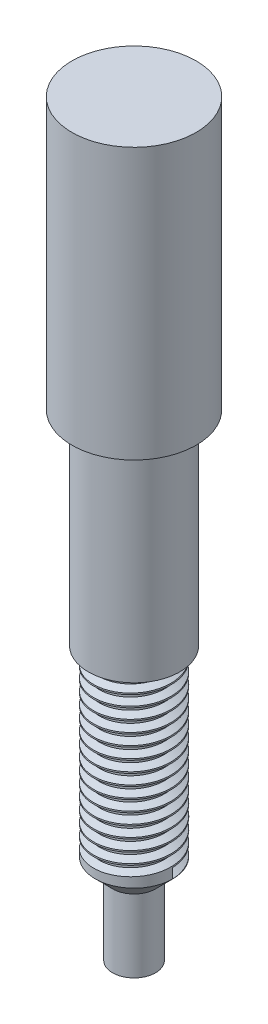
SolidWorks part; units mm, degrees
ref_plane "Front Plane" through (0, 0, 0) normal (0, 0, 1) x (1, 0, 0)
ref_plane "Top Plane" through (0, 0, 0) normal (0, 1, 0) x (1, 0, 0)
ref_plane "Right Plane" through (0, 0, 0) normal (1, 0, 0) x (0, 0, -1)
sketch "Sketch2" plane through (0, 0, 0) normal (0, 0, 1) x (1, 0, 0)
  line L0 (0, 0) -> (0, 508.8276) construction
  line L1 (0, 0) -> (6, 0)
  line L2 (0, 0) -> (0, 25.4)
  line L3 (0, 25.4) -> (6, 25.4)
  line L4 (6, 0) -> (6, 25.4)
  line L5 (0, 25.4) -> (10.8102, 25.4)
  line L6 (0, 25.4) -> (0, 76.2)
  line L7 (0, 76.2) -> (10.8102, 76.2)
  line L8 (10.8102, 25.4) -> (10.8102, 76.2)
  line L9 (0, 76.2) -> (12.7635, 76.2)
  line L10 (0, 76.2) -> (0, 133.35)
  line L11 (0, 133.35) -> (12.7635, 133.35)
  line L12 (12.7635, 76.2) -> (12.7635, 133.35)
  line L13 (0, 133.35) -> (17.3461, 133.35)
  line L14 (0, 133.35) -> (0, 209.042)
  line L15 (0, 209.042) -> (17.3461, 209.042)
  line L16 (17.3461, 133.35) -> (17.3461, 209.042)
  dimension "D1" = 75.692
  dimension "D2" = 17.3461
  dimension "D4" = 57.15
  dimension "D3" = 12.7635
  dimension "D5" = 50.8
  dimension "D6" = 10.8102
  dimension "D7" = 25.4
  dimension "D8" = 6
revolve "Revolve1" add sketch "Sketch2" angle 360 about L0 region at (3, 12.7, 0) region at (5.4051, 50.8, 0) region at (6.3817, 104.775, 0) region at (8.673, 171.196, 0)
chamfer "Chamfer1" distance 5.08 angle 45 1 edges at (0, 25.4, -6)
thread "Thread1" pitch 3.175 method cut profile "Thread Profile1" start angle 0, offset 0, length 0, pitch 3.175, diameter 21.6205
ref_plane "Plane1" through (10.8102, 25.1302, 0) normal (0, 0, 1) x (1, 0, 0)
sketch "Thread Profile1" plane through (10.8102, 25.1302, 0) normal (0, 0, 1) x (1, 0, 0)
  line L0 (0, 0) -> (0, 3.175) construction
  line L11 (0, 0) -> (0, 2.7781)
  line L12 (0, 2.7781) -> (-1.7185, 1.7859)
  line L13 (-1.7185, 1.7859) -> (-1.7185, 0.9922)
  line L15 (-1.7185, 0.9922) -> (0, 0)
  line L17 (-1.7185, 1.3891) -> (0, 1.3891) construction
  point P2 (0, 0)
  dimension "Pitch" = 3.175
  dimension "Profile_Angle" = 60
  dimension "Profile_Land" = 0.7937
  dimension "Profile_Height" = 1.7185
equation "\"hole diamiter\"= 1.36in"
equation "\"wheel depth\"= 2.88"
equation "\"press_to_wheel\" = 0.005 * sqr ( \"hole diamiter\" )"
equation "\"wheel_connection\"= \"hole diamiter\" + \"press_to_wheel\"'https://at-machining.com/tolerance-press-fit/"
equation "\"D1@Sketch2\"=\"wheel depth\"+0.1"
equation "\"D2@Sketch2\"=\"wheel_connection\"/2"
equation "\"fitting depth\" = 2.25"
equation "\"D4@Sketch2\"=\"fitting depth\""
equation "\"bearing_id\"= 1"
equation "\"bearing_connection\"= 0.005 * sqr ( \"bearing_id\" ) + \"bearing_id\"'https://at-machining.com/tolerance-press-fit/"
equation "\"D3@Sketch2\"=\"bearing_connection\"/2"
equation "\"thread length\" = 2"
equation "\"minor_diamiter\"= 0.8512in'https://www.machiningdoctor.com/threadinfo/?tid=109"
equation "\"D5@Sketch2\"=\"thread length\""
equation "\"D6@Sketch2\"=\"minor_diamiter\"/2"
equation "\"coupling diamiter\"= 12mm"
equation "\"coupling lenght\"=1"
equation "\"D7@Sketch2\"=\"coupling lenght\""
equation "\"D8@Sketch2\"=\"coupling diamiter\"/2"
